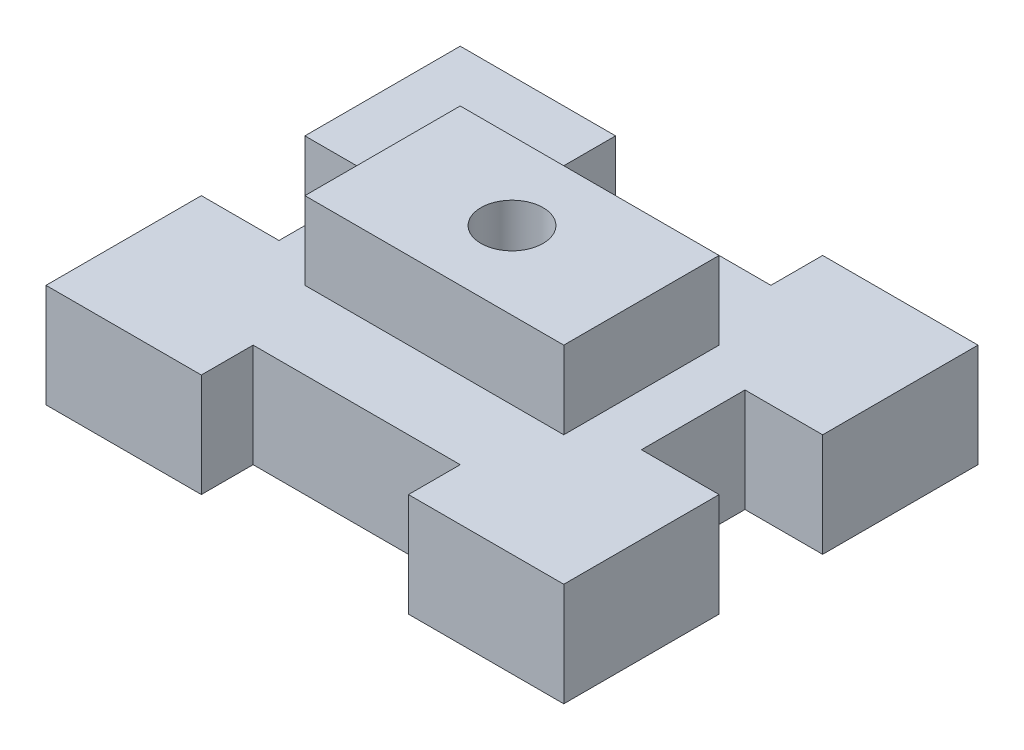
SolidWorks part; units mm, degrees
ref_plane "Front Plane" through (0, 0, 0) normal (0, 0, 1) x (1, 0, 0)
ref_plane "Top Plane" through (0, 0, 0) normal (0, 1, 0) x (1, 0, 0)
ref_plane "Right Plane" through (0, 0, 0) normal (1, 0, 0) x (0, 0, -1)
sketch "Sketch1" plane through (0, 0, 0) normal (0, 1, 0) x (1, 0, 0)
  line L4 (0, 0) -> (30, 0)
  line L5 (30, 0) -> (30, -10)
  line L6 (30, -10) -> (70, -10)
  line L7 (70, -10) -> (70, 0)
  line L8 (70, 0) -> (100, 0)
  line L9 (100, 0) -> (100, -30)
  line L10 (100, -30) -> (85, -30)
  line L11 (85, -30) -> (85, -50)
  line L12 (85, -50) -> (100, -50)
  line L13 (100, -50) -> (100, -80)
  line L14 (100, -80) -> (70, -80)
  line L15 (70, -80) -> (70, -70)
  line L16 (70, -70) -> (30, -70)
  line L17 (30, -70) -> (30, -80)
  line L18 (30, -80) -> (0, -80)
  line L19 (0, -80) -> (0, -50)
  line L20 (0, -50) -> (15, -50)
  line L21 (15, -50) -> (15, -30)
  line L22 (15, -30) -> (0, -30)
  line L23 (0, -30) -> (0, 0)
  point P14 (70, -59.0282)
  dimension "D1" = 40
  dimension "D2" = 100
  dimension "D3" = 10
  dimension "D4" = 15
  dimension "D5" = 30
  dimension "D6" = 80
extrude "Boss-Extrude1" add sketch "Sketch1" along normal blind 10 and the other way blind 10
sketch "Sketch2" plane through (0, 0, 0) normal (0, 1, 0) x (1, 0, 0)
  line L0 (25, -25) -> (25, -55)
  line L1 (25, -55) -> (75, -55)
  line L2 (75, -55) -> (75, -25)
  line L3 (75, -25) -> (25, -25)
  line L6 (0, 0) -> (0, -30) construction
  line L7 (0, -80) -> (30, -80) construction
  point P6 (50, -25)
  point P7 (25, -40)
  point P10 (50, -40)
  dimension "D1" = 50
  dimension "D2" = 30
  dimension "D3" = 50
  dimension "D4" = 40
extrude "Boss-Extrude2" add sketch "Sketch2" along normal blind 25 and the other way blind 25
sketch "Sketch3" plane through (0, 25, 0) normal (0, 1, 0) x (1, 0, 0)
  line L0 (25, -25) -> (25, -55) construction
  line L1 (25, -55) -> (75, -55) construction
  circle A0 centre (50, -40) radius 6
  dimension "D1" = 12
  dimension "D2" = 25
  dimension "D3" = 15
extrude "Cut-Extrude1" cut sketch "Sketch3" against normal through all
